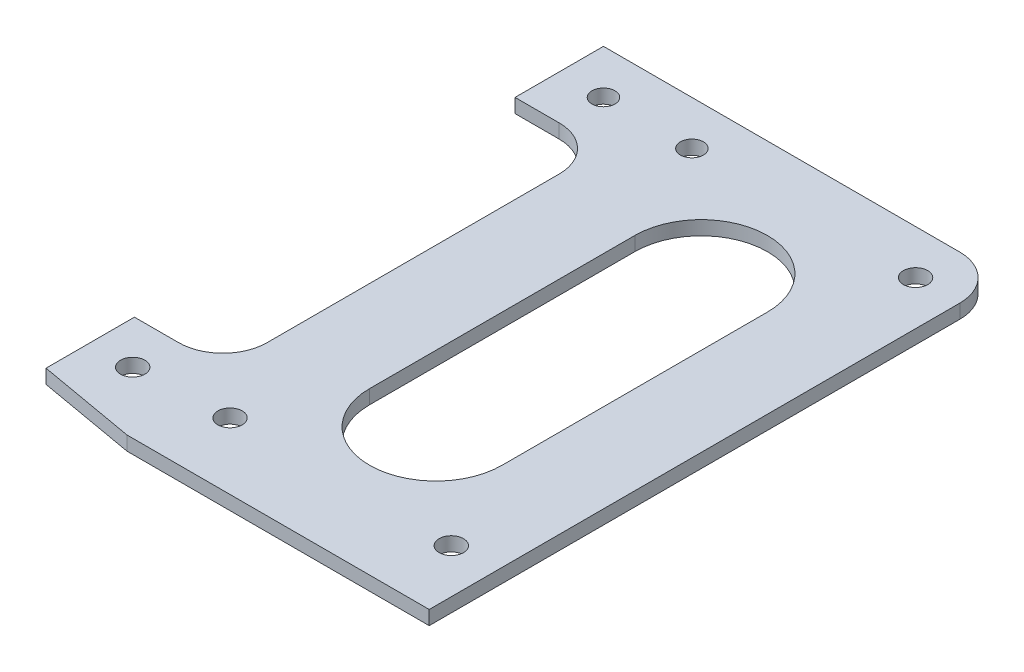
SolidWorks part; units mm, degrees
ref_plane "Front Plane" through (0, 0, 0) normal (0, 0, 1) x (1, 0, 0)
ref_plane "Top Plane" through (0, 0, 0) normal (0, 1, 0) x (1, 0, 0)
ref_plane "Right Plane" through (0, 0, 0) normal (1, 0, 0) x (0, 0, -1)
ref_plane "Plane1" through (0, 32.1347, 0) normal (0, -1, 0) x (1, 0, 0)
sketch "Sketch11" plane through (0, 32.1347, 0) normal (0, -1, 0) x (1, 0, 0)
  line L0 (-82.6713, -32.35) -> (-104.9222, -36.2734)
  line L1 (-104.9222, -36.2734) -> (-104.9222, -162.35)
  line L2 (-104.9222, -162.35) -> (-24.3331, -162.35)
  line L3 (-14.3331, -152.35) -> (-14.3331, -32.35)
  line L4 (-14.3331, -32.35) -> (-82.6713, -32.35)
  arc A0 (-24.3331, -162.35) -> (-14.3331, -152.35) centre (-24.3331, -152.35) ccw
base flange "Base-Flange1" sketch "Sketch11" thickness 3.175 reverse thickness direction yes parameters "D1"=0
sketch "Sketch16" plane through (0, 35.3097, 0) normal (0, 1, 0) x (-1, 0, 0)
  line L0 (104.9222, -142.35) -> (104.9222, -56.2734)
  line L1 (104.9222, -56.2734) -> (94.9222, -56.2734)
  line L2 (84.9222, -66.2734) -> (84.9222, -132.35)
  line L3 (94.9222, -142.35) -> (104.9222, -142.35)
  arc A0 (94.9222, -56.2734) -> (84.9222, -66.2734) centre (94.9222, -66.2734) ccw
  arc A1 (84.9222, -132.35) -> (94.9222, -142.35) centre (94.9222, -132.35) ccw
extrude "Cut-Extrude1" cut sketch "Sketch16" against normal through all
sketch "Sketch17" plane through (0, 35.3097, 0) normal (0, 1, 0) x (-1, 0, 0)
  line L0 (64.3331, -128.85) -> (64.3331, -68.85)
  line L1 (34.3331, -68.85) -> (34.3331, -128.85)
  arc A0 (34.3331, -128.85) -> (64.3331, -128.85) centre (49.3331, -128.85) ccw
  arc A1 (64.3331, -68.85) -> (34.3331, -68.85) centre (49.3331, -68.85) ccw
extrude "Cut-Extrude2" cut sketch "Sketch17" against normal through all
hole_wizard "Ø5.2 (5.2) Diameter Hole1" positions "Sketch19" profile "Sketch18" hole size "Ø5.2" standard "ANSI Metric"
sketch "Sketch19" plane through (0, 32.1347, 0) normal (0, -1, 0) x (-1, 0, 0)
  point P0 (94.9222, 152.35)
  point P1 (74.9222, 152.35)
sketch "Sketch18" plane through (-94.9222, 32.1347, -152.35) normal (1, 0, 0) x (0, 0, -1)
  line L0 (0, 0) -> (0, 3.175)
  line L1 (0, 3.175) -> (2.6, 3.175)
  line L2 (2.6, 3.175) -> (2.6, 0)
  line L5 (2.6, 0) -> (0, 0)
  line L11 (0, -6.35) -> (0, 107.95) construction
  dimension "Thru Hole Dia." = 5.2
  dimension "Thru Hole Depth" = 3.175
hole_wizard "Ø5.5 (5.5) Diameter Hole1" positions "Sketch21" profile "Sketch20" hole size "Ø5.5" standard "ANSI Metric"
sketch "Sketch21" plane through (0, 32.1347, 0) normal (0, -1, 0) x (-1, 0, 0)
  point P0 (95.3161, 46.2734)
  point P1 (74.3755, 47.35)
  point P2 (24.3331, 47.35)
  point P3 (24.3331, 152.35)
sketch "Sketch20" plane through (-95.3161, 32.1347, -46.2734) normal (1, 0, 0) x (0, 0, -1)
  line L0 (0, 0) -> (0, 3.175)
  line L1 (0, 3.175) -> (2.75, 3.175)
  line L2 (2.75, 3.175) -> (2.75, 0)
  line L5 (2.75, 0) -> (0, 0)
  line L11 (0, -6.35) -> (0, 107.95) construction
  dimension "Thru Hole Dia." = 5.5
  dimension "Thru Hole Depth" = 3.175
sketch "Bend-Lines4" plane through (0, 0, 0) normal (0, 1, 0) x (1, 0, 0)
sketch "Bounding-Box4" plane through (0, 0, 0) normal (0, 1, 0) x (1, 0, 0)
sheet metal parameters "Sheet-Metal(5)" thickness 3.175 parameters "D1"=0
flat pattern "Flat-Pattern(5)" [suppressed]
sketch "Bend-Lines5" plane through (0, 0, 0) normal (0, 1, 0) x (1, 0, 0)
sketch "Bounding-Box5" [suppressed] plane through (0, 0, 0) normal (0, 1, 0) x (1, 0, 0)
sheet metal parameters "Sheet-Metal(6)" thickness 3.175 parameters "D1"=0
flat pattern "Flat-Pattern(5)"
sketch "Bend-Lines5" plane through (0, 0, 0) normal (0, 1, 0) x (1, 0, 0)
sketch "Bounding-Box5" [suppressed] plane through (0, 0, 0) normal (0, 1, 0) x (1, 0, 0)
sheet metal parameters "Sheet-Metal(7)" thickness 3.175 parameters "D1"=0
flat pattern "Flat-Pattern(5)"
sketch "Bend-Lines5" plane through (0, 0, 0) normal (0, 1, 0) x (1, 0, 0)
sketch "Bounding-Box5" [suppressed] plane through (0, 0, 0) normal (0, 1, 0) x (1, 0, 0)
sheet metal parameters "Sheet-Metal(8)" thickness 3.175 parameters "D1"=0
flat pattern "Flat-Pattern(5)"
sketch "Bend-Lines5" plane through (0, 0, 0) normal (0, 1, 0) x (1, 0, 0)
sketch "Bounding-Box5" [suppressed] plane through (0, 0, 0) normal (0, 1, 0) x (1, 0, 0)
sheet metal parameters "Sheet-Metal(9)" thickness 3.175 parameters "D1"=0
flat pattern "Flat-Pattern(5)"
sketch "Bend-Lines5" plane through (0, 0, 0) normal (0, 1, 0) x (1, 0, 0)
sketch "Bounding-Box5" [suppressed] plane through (0, 0, 0) normal (0, 1, 0) x (1, 0, 0)
